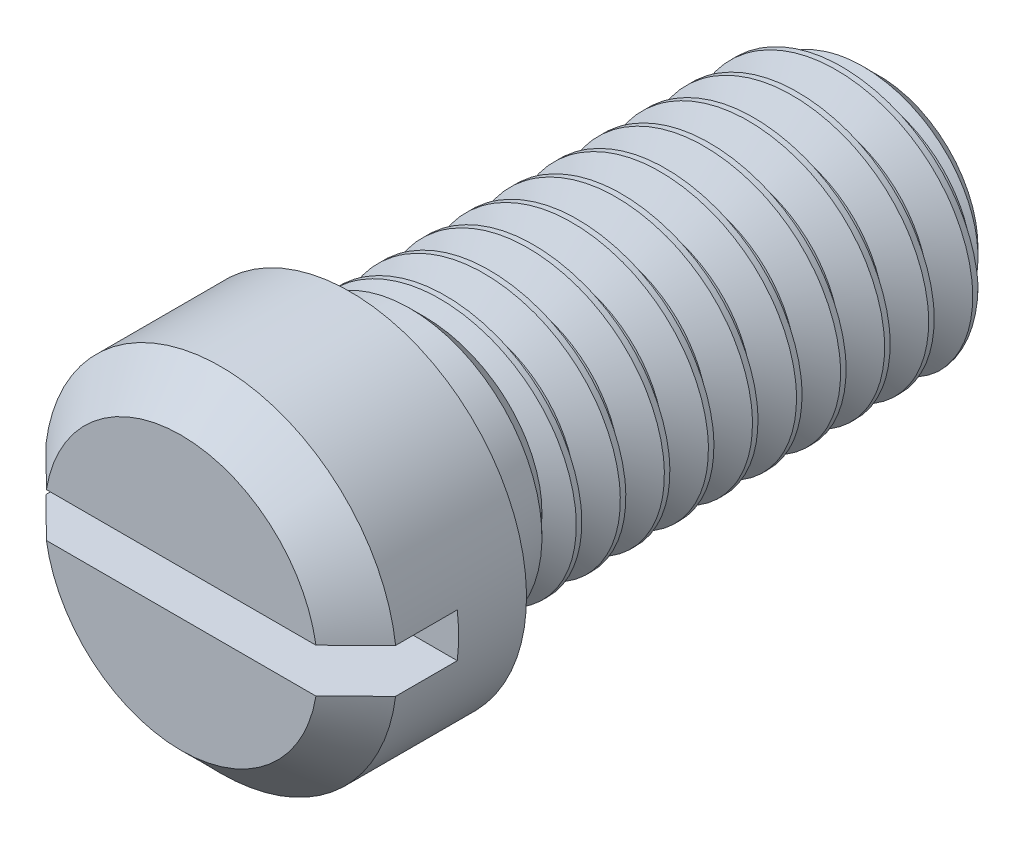
SolidWorks part; units mm, degrees
ref_plane "Front Plane" through (0, 0, 0) normal (0, 0, 1) x (1, 0, 0)
ref_plane "Top Plane" through (0, 0, 0) normal (0, 1, 0) x (1, 0, 0)
ref_plane "Right Plane" through (0, 0, 0) normal (1, 0, 0) x (0, 0, -1)
sketch "Sketch1" plane through (0, 0, 0) normal (1, 0, 0) x (0, 0, -1)
  line L0 (-3.96, 0) -> (3.96, 0) construction
  line L1 (-3.96, 2) -> (-3.96, -2) construction
  line L3 (3.96, 1.5) -> (3.96, -1.5) construction
  line L4 (3.9288, 1.5541) -> (4.4288, 1.5541) construction
  line L5 (-3.96, 0.25) -> (-2.81, 0.25) construction
  line L6 (-3.96, 0.25) -> (-3.96, -0.25) construction
  line L7 (-3.96, -0.25) -> (-2.81, -0.25) construction
  line L8 (-2.81, 0.25) -> (-2.81, -0.25) construction
  line L9 (4.4288, 1.5541) -> (4.1788, 1.1211) construction
  line L10 (4.1788, 1.1211) -> (3.9288, 1.5541) construction
  line L11 (3.9444, 1.5271) -> (4.4131, 1.5271) construction
  line L12 (3.96, 1.5) -> (4.3975, 1.5) construction
  line L13 (4.1475, 1.1752) -> (4.21, 1.1752) construction
  line L14 (4.1788, 1.1752) -> (4.1788, 1.1211) construction
  line L15 (4.1788, 1.5) -> (4.1788, 1.5541) construction
  line L16 (-2.04, 2) -> (-2.04, 1.6) construction
  line L17 (-1.94, 1.5) -> (-1.04, 1.5) construction
  arc A0 (-2.04, 1.6) -> (-1.94, 1.5) centre (-1.94, 1.6) ccw construction
  point P2 (0, 0)
  point P6 (-3.96, 0)
  point P7 (-2.04, 0)
  point P8 (3.96, 0)
  point P10 (-1.04, 0)
  point P11 (3.21, -1.5)
  point P14 (3.96, 0)
  point P21 (-3.96, 0)
  point P28 (-3.51, 0)
  point P35 (4.1788, 1.5271)
  dimension "R" = 0.1
  dimension "Head Diameter" = 4
  dimension "Head Height" = 1.92
  dimension "Thread Size" = 3
  dimension "T" = 1.15
  dimension "N" = 0.5
  dimension "F" = 0.45
  dimension "Length" = 6
  dimension "A" = 1
  dimension "D1" = 0.75
  dimension "D2" = 60
  dimension "Thread Pitch" = 0.5
  dimension "D3" = 0.0625
sketch "Sketch2" plane through (0, 0, 0) normal (1, 0, 0) x (0, 0, -1)
  line L0 (-3.96, 0) -> (3.96, 0)
  line L2 (-2.04, 2) -> (-2.04, 1.6)
  line L7 (-3.96, 1.55) -> (-3.96, 0)
  line L8 (-3.96, 2) -> (-3.96, -2) construction
  line L9 (-3.96, 1.55) -> (-3.51, 2)
  line L10 (-3.51, 2) -> (-2.04, 2)
  line L11 (-1.94, 1.5) -> (3.96, 1.5)
  line L12 (3.96, 1.5) -> (3.96, 0)
  arc A4 (-2.04, 1.6) -> (-1.94, 1.5) centre (-1.94, 1.6) ccw
  arc A5 (-2.04, 1.6) -> (-1.94, 1.5) centre (-1.94, 1.6) ccw construction
  dimension "D3" = 45
revolve "Revolve1" add sketch "Sketch2" angle 360 about L0
chamfer "Chamfer1" distance 0.375 angle 45 1 edges at (0, -1.5, -3.96)
sketch "Sketch3" plane through (0, 0, 0) normal (1, 0, 0) x (0, 0, -1)
  line L4 (-3.96, 0.25) -> (-2.81, 0.25)
  line L5 (-3.96, 0.25) -> (-3.96, -0.25)
  line L6 (-3.96, -0.25) -> (-2.81, -0.25)
  line L7 (-2.81, 0.25) -> (-2.81, -0.25)
extrude "Cut-Extrude1" cut sketch "Sketch3" against normal through all both and the other way through all
sketch "Sketch7" plane through (0, 0, 0) normal (0, 0, 1) x (1, 0, 0)
  circle A0 centre (0, 0) radius 2
  circle A2 centre (0, 0) radius 2 construction
ref_plane "Plane1" through (0, 0, 1.94) normal (0, 0, 1) x (1, 0, 0)
split "Split1" trim tools "Plane1" bodies to split 103 resulting bodies 110 111
sketch "Sketch4" plane through (0, 0, 0) normal (1, 0, 0) x (0, 0, -1)
  line L8 (3.9444, 1.5271) -> (4.4131, 1.5271)
  line L9 (4.4131, 1.5271) -> (4.21, 1.1752)
  line L10 (4.21, 1.1752) -> (4.1475, 1.1752)
  line L11 (4.1475, 1.1752) -> (3.9444, 1.5271)
sketch "Sketch5" plane through (0, 0, -3.96) normal (0, 0, -1) x (-1, 0, 0)
  circle A0 centre (0, 0) radius 1.5
  circle A1 centre (0, 0) radius 1.5 construction
curve "Helix/Spiral1" pitch 0.5 height 6.5 radius 1.5 centre (0, 0, -3.96) axis (0, 0, 1) start towards (0, 1, 0)
sweep "Cut-Sweep4" cut profiles "Sketch4" path "Helix/Spiral1" align with end faces yes
sketch "Sketch8" plane through (0, 0, 0) normal (1, 0, 0) x (0, 0, -1)
  line L0 (-1.94, 1.5) -> (-1.94, 0)
  line L1 (-1.94, -1.5) -> (-1.94, 1.5) construction
  line L2 (-1.94, 0) -> (-1.04, 0)
  line L3 (-1.04, 0) -> (-1.04, 1.1752)
  line L4 (-1.04, 1.1752) -> (-1.3648, 1.5)
  line L5 (-1.3648, 1.5) -> (-1.94, 1.5)
  dimension "D1" = 45
revolve "Revolve2" add sketch "Sketch8" angle 360 about L0
equation "\"D3@Helix/Spiral1\"=\"Length@Sketch1\" + \"Thread Pitch@Sketch1\""
equation "\"D1@Chamfer1\"=\"Thread Pitch@Sketch1\"*.75"
equation "\"D3@Sketch1\"=\"Thread Pitch@Sketch1\"/8"
equation "\"D4@Helix/Spiral1\"=\"Thread Pitch@Sketch1\""
equation "\"D1@Sketch1\"=\"Thread Pitch@Sketch1\"*1.5"
